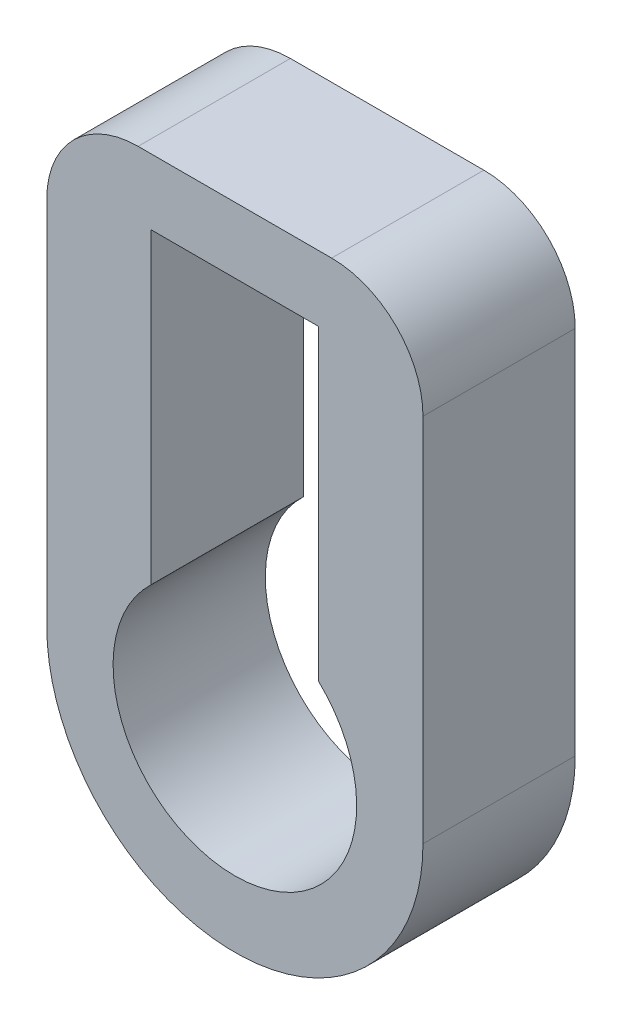
SolidWorks part; units mm, degrees
ref_plane "Front Plane" through (0, 0, 0) normal (0, 0, 1) x (1, 0, 0)
ref_plane "Top Plane" through (0, 0, 0) normal (0, 1, 0) x (1, 0, 0)
ref_plane "Right Plane" through (0, 0, 0) normal (1, 0, 0) x (0, 0, -1)
sketch "Sketch1" plane through (0, 0, 0) normal (0, 0, 1) x (1, 0, 0)
  line L1 (-0.6985, 3.302) -> (0.6985, 3.302)
  line L2 (-0.6985, 3.302) -> (-0.6985, 0)
  line L3 (-0.6985, 0) -> (0.6985, 0)
  line L4 (0.6985, 3.302) -> (0.6985, 0)
  line L5 (-1.569, 0) -> (1.569, 0)
  line L6 (-1.569, 0) -> (-1.569, 3.8505)
  line L7 (-1.569, 3.8505) -> (1.569, 3.8505)
  line L8 (1.569, 0) -> (1.569, 3.8505)
  circle A0 centre (0, 0) radius 0.6985
  circle A1 centre (0, 0) radius 1.569
  point P12 (1.8233, 0)
  point P13 (1.569, 0)
  point P14 (0, 0)
extrude "Boss-Extrude1" add sketch "Sketch1" along normal blind 1.27 contours A1 L8 L7 L6 L2 L1 L4 | L5 A1 A0 | L5 A1 L4 | L2 A1 L5 region at (-0.7482, 2.3535, 0) region at (-1.0566, 0.5538, 0) region at (1.0566, 0.5538, 0) region at (0, -0.7572, 0)
sketch "Sketch2" plane through (0, 0, 0) normal (0, 0, -1) x (-1, 0, 0)
  circle A0 centre (0, 0) radius 1.016
extrude "Cut-Extrude1" cut sketch "Sketch2" against normal blind 2.54
fillet "Fillet2" radius 0.762 2 edges at (-1.569, 3.8505, 0.635) (1.569, 3.8505, 0.635)
